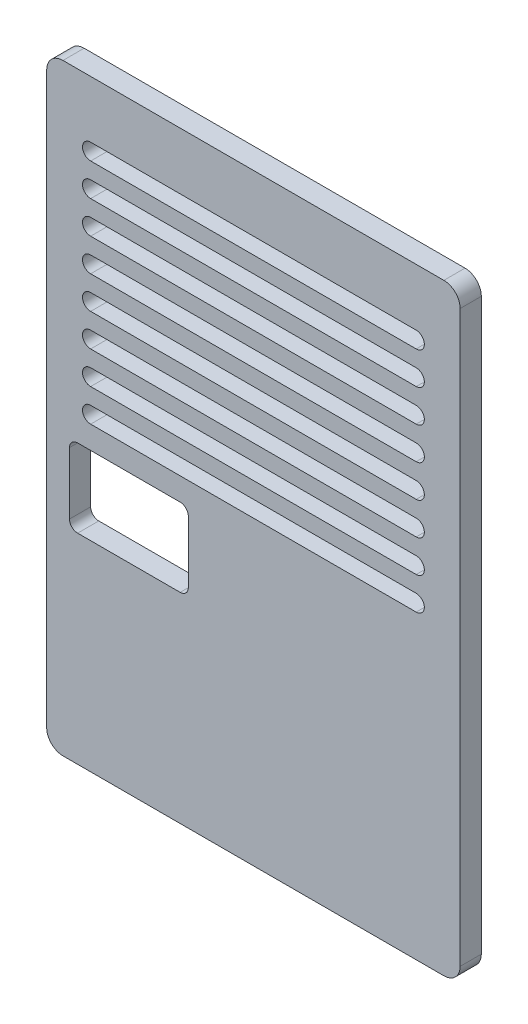
SolidWorks part; units mm, degrees
ref_plane "Front Plane" through (0, 0, 0) normal (0, 0, 1) x (1, 0, 0)
ref_plane "Top Plane" through (0, 0, 0) normal (0, 1, 0) x (1, 0, 0)
ref_plane "Right Plane" through (0, 0, 0) normal (1, 0, 0) x (0, 0, -1)
sketch "Sketch1" plane through (0, 0, 0) normal (0, 0, 1) x (1, 0, 0)
  line L1 (-31.75, 46.25) -> (31.75, 46.25)
  line L2 (-31.75, 46.25) -> (-31.75, -46.25)
  line L3 (-31.75, -46.25) -> (31.75, -46.25)
  line L4 (31.75, 46.25) -> (31.75, -46.25)
  line L16 (-27, 43.9) -> (-13.75, 43.9)
  line L17 (-13.4, 44.25) -> (-13.4, 45)
  line L18 (-13.75, 45.35) -> (-28, 45.35)
  line L19 (-30.85, 42.5) -> (-30.85, 39.25)
  line L20 (-30.5, 38.9) -> (-29.75, 38.9)
  line L21 (-29.4, 39.25) -> (-29.4, 41.5)
  line L22 (-27, 43.9) -> (-13.75, 43.9)
  line L23 (-13.4, 44.25) -> (-13.4, 45)
  line L24 (-13.75, 45.35) -> (-28, 45.35)
  line L25 (-30.85, 42.5) -> (-30.85, 39.25)
  line L26 (-30.5, 38.9) -> (-29.75, 38.9)
  line L27 (-29.4, 39.25) -> (-29.4, 41.5)
  line L38 (30.85, -42.5) -> (30.85, 42.5)
  line L39 (28, 45.35) -> (13.75, 45.35)
  line L40 (13.4, 45) -> (13.4, 44.25)
  line L41 (13.75, 43.9) -> (27, 43.9)
  line L42 (29.4, 41.5) -> (29.4, -41.5505)
  line L44 (27.4, -44.1963) -> (27.4, -45)
  line L46 (30.85, -42.5) -> (30.85, 42.5)
  line L47 (28, 45.35) -> (13.75, 45.35)
  line L48 (13.4, 45) -> (13.4, 44.25)
  line L49 (13.75, 43.9) -> (27, 43.9)
  line L50 (29.4, 41.5) -> (29.4, -41.5505)
  line L52 (27.4, -44.1963) -> (27.4, -45)
  line L58 (-29.4, -41.5505) -> (-29.4, -3.25)
  line L59 (-29.75, -2.9) -> (-30.5, -2.9)
  line L60 (-30.85, -3.25) -> (-30.85, -42.5)
  line L62 (-27.4, -45) -> (-27.4, -44.1963)
  line L64 (-29.4, -41.5505) -> (-29.4, -3.25)
  line L65 (-29.75, -2.9) -> (-30.5, -2.9)
  line L66 (-30.85, -3.25) -> (-30.85, -42.5)
  line L68 (-27.4, -45) -> (-27.4, -44.1963)
  line L145 (-28, -45.35) -> (-27.75, -45.35)
  line L146 (-28, -45.35) -> (-27.75, -45.35)
  line L147 (27.75, -45.35) -> (28, -45.35)
  line L148 (27.75, -45.35) -> (28, -45.35)
  line L225 (-31.75, 43.75) -> (-31.75, 39.25) construction
  line L226 (-13.75, 46.25) -> (-29.25, 46.25) construction
  line L227 (27.75, -46.25) -> (29.25, -46.25) construction
  line L228 (31.75, -43.75) -> (31.75, 43.75) construction
  arc A23 (-29.75, 38.9) -> (-29.4, 39.25) centre (-29.75, 39.25) ccw
  arc A25 (-29.75, 38.9) -> (-29.4, 39.25) centre (-29.75, 39.25) ccw
  arc A27 (-27, 43.9) -> (-29.4, 41.5) centre (-27, 41.5) ccw
  arc A29 (-27, 43.9) -> (-29.4, 41.5) centre (-27, 41.5) ccw
  arc A31 (-13.75, 43.9) -> (-13.4, 44.25) centre (-13.75, 44.25) ccw
  arc A33 (-13.75, 43.9) -> (-13.4, 44.25) centre (-13.75, 44.25) ccw
  arc A35 (-13.4, 45) -> (-13.75, 45.35) centre (-13.75, 45) ccw
  arc A37 (-13.4, 45) -> (-13.75, 45.35) centre (-13.75, 45) ccw
  arc A39 (-28, 45.35) -> (-30.85, 42.5) centre (-28, 42.5) ccw
  arc A41 (-28, 45.35) -> (-30.85, 42.5) centre (-28, 42.5) ccw
  arc A43 (-30.85, 39.25) -> (-30.5, 38.9) centre (-30.5, 39.25) ccw
  arc A45 (-30.85, 39.25) -> (-30.5, 38.9) centre (-30.5, 39.25) ccw
  arc A47 (-29.4, -3.25) -> (-29.75, -2.9) centre (-29.75, -3.25) ccw
  arc A49 (-29.4, -3.25) -> (-29.75, -2.9) centre (-29.75, -3.25) ccw
  arc A51 (27.4, -45) -> (27.75, -45.35) centre (27.75, -45) ccw
  arc A53 (27.4, -45) -> (27.75, -45.35) centre (27.75, -45) ccw
  arc A55 (28, -45.35) -> (30.85, -42.5) centre (28, -42.5) ccw
  arc A57 (28, -45.35) -> (30.85, -42.5) centre (28, -42.5) ccw
  arc A58 (30.85, 42.5) -> (28, 45.35) centre (28, 42.5) ccw
  arc A59 (30.85, 42.5) -> (28, 45.35) centre (28, 42.5) ccw
  arc A60 (13.75, 45.35) -> (13.4, 45) centre (13.75, 45) ccw
  arc A61 (13.75, 45.35) -> (13.4, 45) centre (13.75, 45) ccw
  arc A62 (13.4, 44.25) -> (13.75, 43.9) centre (13.75, 44.25) ccw
  arc A63 (13.4, 44.25) -> (13.75, 43.9) centre (13.75, 44.25) ccw
  arc A64 (29.4, 41.5) -> (27, 43.9) centre (27, 41.5) ccw
  arc A65 (29.4, 41.5) -> (27, 43.9) centre (27, 41.5) ccw
  arc A66 (27.6545, -43.8595) -> (29.4, -41.5505) centre (27, -41.5505) ccw
  arc A67 (27.6545, -43.8595) -> (29.4, -41.5505) centre (27, -41.5505) ccw
  arc A68 (27.6545, -43.8595) -> (27.4, -44.1963) centre (27.75, -44.1963) ccw
  arc A69 (27.6545, -43.8595) -> (27.4, -44.1963) centre (27.75, -44.1963) ccw
  arc A70 (-30.5, -2.9) -> (-30.85, -3.25) centre (-30.5, -3.25) ccw
  arc A71 (-30.5, -2.9) -> (-30.85, -3.25) centre (-30.5, -3.25) ccw
  arc A72 (-30.85, -42.5) -> (-28, -45.35) centre (-28, -42.5) ccw
  arc A73 (-30.85, -42.5) -> (-28, -45.35) centre (-28, -42.5) ccw
  arc A74 (-27.75, -45.35) -> (-27.4, -45) centre (-27.75, -45) ccw
  arc A75 (-27.75, -45.35) -> (-27.4, -45) centre (-27.75, -45) ccw
  arc A76 (-27.4, -44.1963) -> (-27.6545, -43.8595) centre (-27.75, -44.1963) ccw
  arc A77 (-27.4, -44.1963) -> (-27.6545, -43.8595) centre (-27.75, -44.1963) ccw
  arc A78 (-29.4, -41.5505) -> (-27.6545, -43.8595) centre (-27, -41.5505) ccw
  arc A79 (-29.4, -41.5505) -> (-27.6545, -43.8595) centre (-27, -41.5505) ccw
  dimension "D1" = 0.1
  dimension "D2" = 0.1
  dimension "D3" = 0.1
extrude "Boss-Extrude1" add sketch "Sketch1" along normal blind 1.5
extrude "Boss-Extrude2" add sketch "Sketch1<2>" along normal blind 1.75 from surface contours L1 L4 L3 L2 starting at face at (0, 0, 1.5)
sketch "Sketch1<2>" plane through (0, 0, 0) normal (0, 0, 1) x (1, 0, 0) same geometry as "Sketch1"
sketch "Sketch3" plane through (0, 0, 3.25) normal (0, 0, 1) x (1, 0, 0)
  line L0 (-31.75, -46.25) -> (-31.75, 46.25) construction
  line L1 (-28.25, -3.5) -> (-10, -3.5)
  line L2 (-28.25, -3.5) -> (-28.25, -15.5)
  line L3 (-28.25, -15.5) -> (-10, -15.5)
  line L4 (-10, -3.5) -> (-10, -15.5)
  line L5 (31.75, -46.25) -> (-31.75, -46.25) construction
  dimension "D1" = 3.5
  dimension "D2" = 30.75
  dimension "D3" = 12
  dimension "D4" = 18.25
extrude "Cut-Extrude1" cut sketch "Sketch3" against normal through all
fillet "Fillet1" radius 2.5 4 edges at (31.75, 46.25, 1.625) (31.75, -46.25, 1.625) (-31.75, -46.25, 1.625) (-31.75, 46.25, 1.625)
fillet "Fillet2" radius 1.25 4 edges at (-10, -3.5, 1.625) (-10, -15.5, 1.625) (-28.25, -15.5, 1.625) (-28.25, -3.5, 1.625)
sketch "Sketch4" plane through (0, 0, 3.25) normal (0, 0, 1) x (1, 0, 0)
  line L0 (-25, 36.25) -> (25, 36.25) construction
  line L1 (-25, 36.25) -> (25, 36.25) construction
  line L2 (-25, 37.5) -> (25, 37.5)
  line L3 (-25, 35) -> (25, 35)
  line L4 (-29.25, 46.25) -> (29.25, 46.25) construction
  line L5 (-25, 31.25) -> (25, 31.25) construction
  line L6 (-25, 32.5) -> (25, 32.5)
  line L7 (-25, 30) -> (25, 30)
  line L8 (-25, 26.25) -> (25, 26.25) construction
  line L9 (-25, 27.5) -> (25, 27.5)
  line L10 (-25, 25) -> (25, 25)
  line L11 (-25, 21.25) -> (25, 21.25) construction
  line L12 (-25, 22.5) -> (25, 22.5)
  line L13 (-25, 20) -> (25, 20)
  line L14 (-25, 16.25) -> (25, 16.25) construction
  line L15 (-25, 17.5) -> (25, 17.5)
  line L16 (-25, 15) -> (25, 15)
  line L17 (-25, 11.25) -> (25, 11.25) construction
  line L18 (-25, 12.5) -> (25, 12.5)
  line L19 (-25, 10) -> (25, 10)
  line L20 (-25, 6.25) -> (25, 6.25) construction
  line L21 (-25, 7.5) -> (25, 7.5)
  line L22 (-25, 5) -> (25, 5)
  line L23 (-25, 1.25) -> (25, 1.25) construction
  line L24 (-25, 2.5) -> (25, 2.5)
  line L25 (-25, 0) -> (25, 0)
  arc A0 (-25, 37.5) -> (-25, 35) centre (-25, 36.25) ccw
  arc A1 (25, 35) -> (25, 37.5) centre (25, 36.25) ccw
  arc A2 (-25, 32.5) -> (-25, 30) centre (-25, 31.25) ccw
  arc A3 (25, 30) -> (25, 32.5) centre (25, 31.25) ccw
  arc A4 (-25, 27.5) -> (-25, 25) centre (-25, 26.25) ccw
  arc A5 (25, 25) -> (25, 27.5) centre (25, 26.25) ccw
  arc A6 (-25, 22.5) -> (-25, 20) centre (-25, 21.25) ccw
  arc A7 (25, 20) -> (25, 22.5) centre (25, 21.25) ccw
  arc A8 (-25, 17.5) -> (-25, 15) centre (-25, 16.25) ccw
  arc A9 (25, 15) -> (25, 17.5) centre (25, 16.25) ccw
  arc A10 (-25, 12.5) -> (-25, 10) centre (-25, 11.25) ccw
  arc A11 (25, 10) -> (25, 12.5) centre (25, 11.25) ccw
  arc A12 (-25, 7.5) -> (-25, 5) centre (-25, 6.25) ccw
  arc A13 (25, 5) -> (25, 7.5) centre (25, 6.25) ccw
  arc A14 (-25, 2.5) -> (-25, 0) centre (-25, 1.25) ccw
  arc A15 (25, 0) -> (25, 2.5) centre (25, 1.25) ccw
  point P2 (0, 36.25)
  point P3 (0, 36.25)
  point P13 (0, 31.25)
  point P23 (0, 26.25)
  point P30 (0, 21.25)
  point P37 (0, 16.25)
  point P44 (0, 11.25)
  point P51 (0, 6.25)
  point P58 (0, 1.25)
  dimension "D1" = 50
  dimension "D2" = 2.5
  dimension "D3" = 10
  dimension "D4" = 8
extrude "Cut-Extrude2" cut sketch "Sketch4" against normal through all
sketch "Sketch5" plane through (0, 0, 0) normal (0, 0, -1) x (-1, 0, 0)
  line L0 (29.25, -46.25) -> (-29.25, -46.25) construction
  line L1 (23.7429, -46.25) -> (-21.4668, -46.25)
  line L2 (23.7429, -46.25) -> (23.7429, -41.25)
  line L3 (23.7429, -41.25) -> (-21.4668, -41.25)
  line L4 (-21.4668, -46.25) -> (-21.4668, -41.25)
  point P4 (0, -46.25)
  point P5 (0, -46.25)
  dimension "D1" = 5
extrude "Boss-Extrude3" add sketch "Sketch5" along normal blind 5.5
fillet "Fillet3" radius 2.5 3 edges at (-1.1381, -41.25, 0) (21.4668, -43.75, 0) (-23.7429, -43.75, 0)
